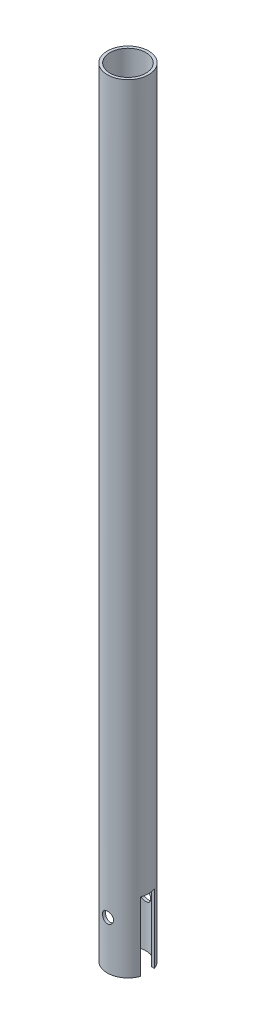
SolidWorks part; units mm, degrees
material "Cast Stainless Steel"
ref_plane "Спереди" through (0, 0, 0) normal (0, 0, 1) x (1, 0, 0)
ref_plane "Сверху" through (0, 0, 0) normal (0, 1, 0) x (1, 0, 0)
ref_plane "Справа" through (0, 0, 0) normal (1, 0, 0) x (0, 0, -1)
other "Configuration Table"
sketch "Sketch1" plane through (0, 0, 0) normal (0, 1, 0) x (1, 0, 0)
  circle A0 centre (0, 0) radius 15
  circle A1 centre (0, 0) radius 13
  dimension "D1" = 30
  dimension "D2" = 2
extrude "Boss-Extrude1" add sketch "Sketch1" along normal mid plane 565
sketch "Sketch3" plane through (0, 0, 0) normal (1, 0, 0) x (0, 0, -1)
  line L0 (-15, -282.5) -> (15, -282.5) construction
  line L1 (-5, -282.5) -> (5, -282.5)
  line L2 (-5, -282.5) -> (-5, -232.5)
  line L3 (-5, -232.5) -> (5, -232.5)
  line L4 (5, -282.5) -> (5, -232.5)
  line L6 (0, 308.2069) -> (0, -341.3903) construction
  dimension "D1" = 10
  dimension "D2" = 50
extrude "Cut-Extrude1" cut sketch "Sketch3" against normal mid plane 565
sketch "Sketch4" plane through (0, 0, 0) normal (0, 0, 1) x (1, 0, 0)
  line L0 (-14.1421, -282.5) -> (14.1421, -282.5) construction
  circle A0 centre (0, -247.5) radius 4
  dimension "D2" = 8
  dimension "D1" = 35
extrude "Cut-Extrude2" cut sketch "Sketch4" against normal through all both and the other way through all
sketch "Sketch6" plane through (0, 0, 0) normal (1, 0, 0) x (0, 0, -1)
  line L0 (0, -238.938) -> (0, -297.1041) construction
  line L1 (-25, -232.5) -> (25, -232.5)
  line L2 (-25, -232.5) -> (-25, -282.5)
  line L3 (-25, -282.5) -> (25, -282.5)
  line L4 (25, -232.5) -> (25, -282.5)
  dimension "D1" = 50
  dimension "D2" = 50
extrude "Cut-Extrude3" [suppressed] cut sketch "Sketch6" against normal through all both and the other way through all
